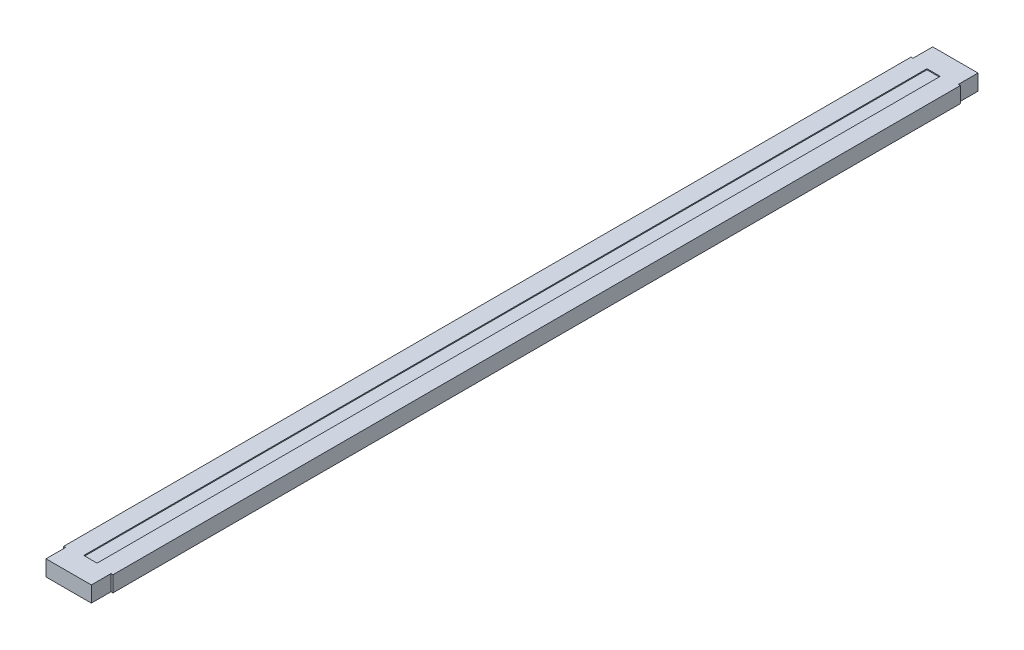
SolidWorks part; units mm, degrees
ref_plane "Front Plane" through (0, 0, 0) normal (0, 0, 1) x (1, 0, 0)
ref_plane "Top Plane" through (0, 0, 0) normal (0, 1, 0) x (1, 0, 0)
ref_plane "Right Plane" through (0, 0, 0) normal (1, 0, 0) x (0, 0, -1)
sketch "Sketch1" plane through (0, 0, 0) normal (0, 0, 1) x (1, 0, 0)
  line L1 (-6.35, -2.032) -> (6.35, -2.032)
  line L2 (-6.35, -2.032) -> (-6.35, 2.032)
  line L3 (-6.35, 2.032) -> (6.35, 2.032)
  line L4 (6.35, -2.032) -> (6.35, 2.032)
  line L5 (-6.35, -2.032) -> (6.35, 2.032) construction
  line L6 (-6.35, 2.032) -> (6.35, -2.032) construction
  point P0 (0, 0)
  dimension "D1" = 4.064
  dimension "D2" = 12.7
extrude "Boss-Extrude1" add sketch "Sketch1" along normal blind 228.6
sketch "Sketch2" plane through (0, 2.032, 0) normal (0, 1, 0) x (1, 0, 0)
  line L0 (1.7145, -114.3) -> (6.35, -114.3) construction
  line L1 (-1.7145, -5.6134) -> (1.7145, -5.6134)
  line L2 (-1.7145, -5.6134) -> (-1.7145, -222.9866)
  line L3 (-1.7145, -222.9866) -> (1.7145, -222.9866)
  line L4 (1.7145, -5.6134) -> (1.7145, -222.9866)
  line L5 (6.35, -228.6) -> (6.35, 0) construction
  line L6 (-1.7145, -114.3) -> (-6.35, -114.3) construction
  line L7 (-6.35, -228.6) -> (-6.35, 0) construction
  dimension "D1" = 3.429
  dimension "D2" = 217.3732
extrude "Cut-Extrude1" cut sketch "Sketch2" against normal blind 0.254
sketch "Sketch3" plane through (0, 2.032, 0) normal (0, 1, 0) x (1, 0, 0)
  line L1 (-6.35, -228.6) -> (-5.842, -228.6)
  line L2 (-6.35, -228.6) -> (-6.35, -223.52)
  line L3 (-6.35, -223.52) -> (-5.842, -223.52)
  line L4 (-5.842, -228.6) -> (-5.842, -223.52)
  dimension "D1" = 0.508
  dimension "D2" = 5.08
extrude "Cut-Extrude2" cut sketch "Sketch3" against normal through all
ref_plane "Plane1" through (0, 0, 114.3) normal (0, 0, -1) x (-1, 0, 0)
mirror "Mirror1" about plane through (0, 0, 114.3) normal (0, 0, -1) of "Cut-Extrude2"
mirror "Mirror2" about plane through (0, 0, 0) normal (1, 0, 0) of "Mirror1", "Cut-Extrude2"
